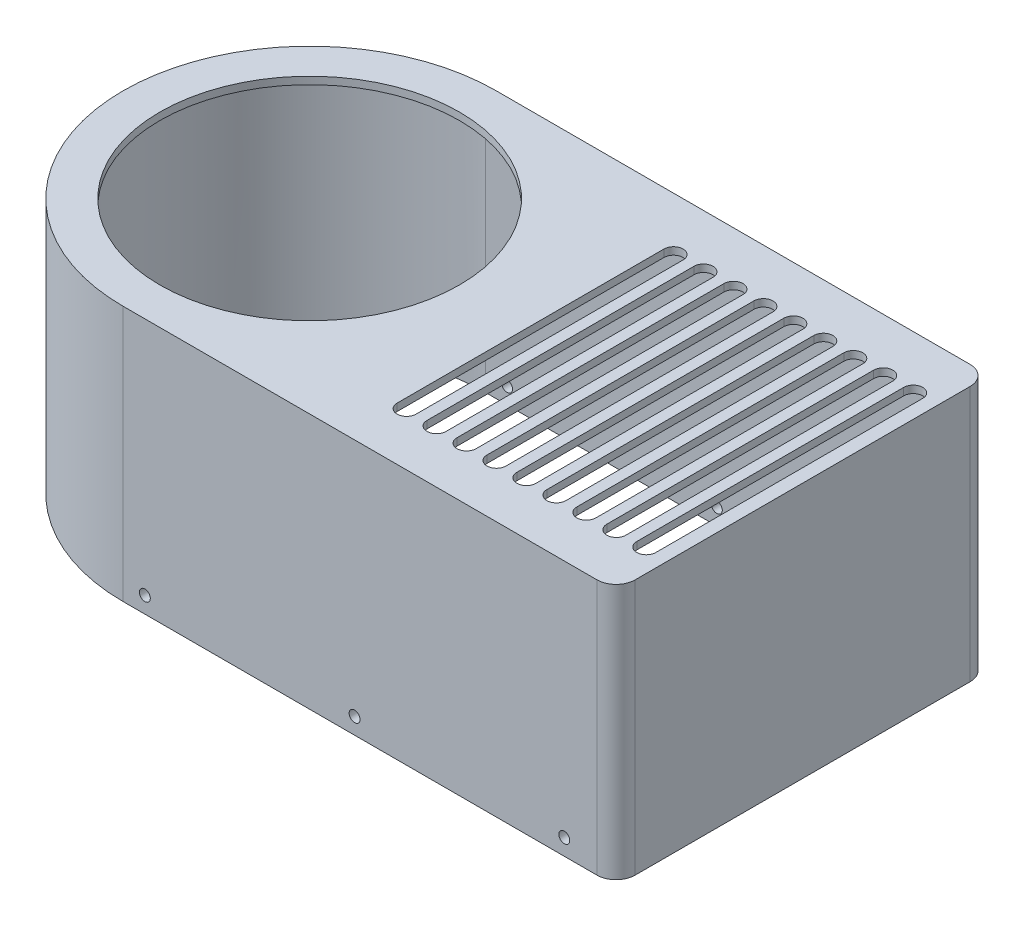
SolidWorks part; units mm, degrees
ref_plane "Front Plane" through (0, 0, 0) normal (0, 0, 1) x (1, 0, 0)
ref_plane "Top Plane" through (0, 0, 0) normal (0, 1, 0) x (1, 0, 0)
ref_plane "Right Plane" through (0, 0, 0) normal (1, 0, 0) x (0, 0, -1)
sketch "Sketch1" plane through (0, 0, 0) normal (0, 1, 0) x (1, 0, 0)
  line L0 (0, 64.5) -> (177, 64.5)
  line L1 (0, -64.5) -> (177, -64.5)
  line L2 (177, 64.5) -> (177, -64.5)
  line L3 (0, -68.5) -> (181, -68.5)
  line L4 (181, -68.5) -> (181, 68.5)
  line L5 (181, 68.5) -> (0, 68.5)
  circle A1 centre (0, 0) radius 25 construction
  arc A2 (0, 64.5) -> (0, -64.5) centre (0, 0) ccw
  arc A4 (0, -68.5) -> (0, 68.5) centre (0, 0) cw
  point P6 (181, 0)
  point P11 (177, 0)
  dimension "D1" = 4
  dimension "D2" = 50
  dimension "D3" = 129
  dimension "D4" = 177
  dimension "D5" = 4
  dimension "D6" = 4
extrude "Boss-Extrude1" add sketch "Sketch1" along normal blind 93.9
sketch "Sketch2" plane through (0, 93.9, 0) normal (0, 1, 0) x (1, 0, 0)
  line L0 (0, -64.5) -> (177, -64.5)
  line L1 (177, -64.5) -> (177, 64.5)
  line L2 (177, 64.5) -> (0, 64.5)
  arc A0 (0, 64.5) -> (0, -64.5) centre (0, 0) ccw
extrude "Boss-Extrude2" add sketch "Sketch2" against normal blind 2.7
fillet "Fillet1" radius 7 2 edges at (181, 46.95, -68.5) (181, 46.95, 68.5)
fillet "Fillet2" radius 7 2 edges at (177, 45.6, 64.5) (177, 45.6, -64.5)
sketch "Sketch3" plane through (0, 93.9, 0) normal (0, 1, 0) x (1, 0, 0)
  line L0 (181, 0) -> (172.6, 0) construction
  line L1 (181, -61.5) -> (181, 61.5) construction
  line L2 (172.6, 49) -> (172.6, -49) construction
  line L3 (176.1, 49) -> (176.1, -49)
  line L4 (169.1, 49) -> (169.1, -49)
  line L5 (150.6, 49) -> (150.6, -49) construction
  line L6 (154.1, 49) -> (154.1, -49)
  line L7 (147.1, 49) -> (147.1, -49)
  line L8 (161.6, 49) -> (161.6, -49) construction
  line L9 (165.1, 49) -> (165.1, -49)
  line L10 (158.1, 49) -> (158.1, -49)
  line L11 (139.6, 49) -> (139.6, -49) construction
  line L12 (143.1, 49) -> (143.1, -49)
  line L13 (136.1, 49) -> (136.1, -49)
  line L14 (161.6, 0) -> (172.6, 0) construction
  line L15 (150.6, 0) -> (161.6, 0) construction
  line L16 (139.6, 0) -> (150.6, 0) construction
  line L17 (128.6, 49) -> (128.6, -49) construction
  line L18 (132.1, 49) -> (132.1, -49)
  line L19 (125.1, 49) -> (125.1, -49)
  line L20 (117.6, 49) -> (117.6, -49) construction
  line L21 (121.1, 49) -> (121.1, -49)
  line L22 (114.1, 49) -> (114.1, -49)
  line L23 (106.6, 49) -> (106.6, -49) construction
  line L24 (110.1, 49) -> (110.1, -49)
  line L25 (103.1, 49) -> (103.1, -49)
  line L26 (95.6, -49) -> (95.6, 49) construction
  line L29 (139.6, 0) -> (128.6, 0) construction
  line L30 (128.6, 0) -> (117.6, 0) construction
  line L31 (117.6, 0) -> (106.6, 0) construction
  line L32 (106.6, 0) -> (95.6, 0) construction
  line L33 (92.1, -49) -> (92.1, 49)
  line L36 (99.1, -49) -> (99.1, 49)
  line L37 (84.6, -49) -> (84.6, 49) construction
  line L38 (81.1, -49) -> (81.1, 49)
  line L39 (88.1, -49) -> (88.1, 49)
  circle A0 centre (0, 0) radius 55
  arc A1 (176.1, 49) -> (169.1, 49) centre (172.6, 49) ccw
  arc A2 (169.1, -49) -> (176.1, -49) centre (172.6, -49) ccw
  arc A3 (154.1, 49) -> (147.1, 49) centre (150.6, 49) ccw
  arc A4 (147.1, -49) -> (154.1, -49) centre (150.6, -49) ccw
  arc A5 (165.1, 49) -> (158.1, 49) centre (161.6, 49) ccw
  arc A6 (158.1, -49) -> (165.1, -49) centre (161.6, -49) ccw
  arc A7 (143.1, 49) -> (136.1, 49) centre (139.6, 49) ccw
  arc A8 (136.1, -49) -> (143.1, -49) centre (139.6, -49) ccw
  arc A9 (132.1, 49) -> (125.1, 49) centre (128.6, 49) ccw
  arc A10 (125.1, -49) -> (132.1, -49) centre (128.6, -49) ccw
  arc A11 (121.1, 49) -> (114.1, 49) centre (117.6, 49) ccw
  arc A12 (114.1, -49) -> (121.1, -49) centre (117.6, -49) ccw
  arc A13 (110.1, 49) -> (103.1, 49) centre (106.6, 49) ccw
  arc A14 (103.1, -49) -> (110.1, -49) centre (106.6, -49) ccw
  arc A19 (92.1, -49) -> (99.1, -49) centre (95.6, -49) ccw
  arc A20 (99.1, 49) -> (92.1, 49) centre (95.6, 49) ccw
  arc A21 (81.1, -49) -> (88.1, -49) centre (84.6, -49) ccw
  arc A22 (88.1, 49) -> (81.1, 49) centre (84.6, 49) ccw
  point P9 (172.6, 0)
  point P17 (150.6, 0)
  point P24 (161.6, 0)
  point P31 (139.6, 0)
  point P40 (128.6, 0)
  point P47 (117.6, 0)
  point P54 (106.6, 0)
  point P61 (95.6, 0)
  point P70 (0, 0)
  point P73 (84.6, 0)
  point P78 (0, 0)
  dimension "D1" = 110
  dimension "D3" = 3.5
  dimension "D6" = 11
  dimension "D2" = 8.4
  dimension "D4" = 98
  dimension "D5" = 11
extrude "Cut-Extrude1" cut sketch "Sketch3" against normal through all
sketch "Sketch5" plane through (0, 91.2, 0) normal (0, -1, 0) x (1, 0, 0)
  line L0 (0, 64.5) -> (23.0651, 64.5)
  line L1 (0, -64.5) -> (23.0651, -64.5)
  arc A3 (0, -64.5) -> (0, 64.5) centre (0, 0) ccw
  arc A5 (23.0651, -64.5) -> (23.0651, 64.5) centre (0, 0) ccw
extrude "Boss-Extrude3" add sketch "Sketch5" along normal blind 7
chamfer "Chamfer1" distance 0.4 angle 45 2 edges at (68.5, 84.2, 0) (64.5, 84.2, 0)
sketch "Sketch9" plane through (0, 0, 64.5) normal (0, 0, -1) x (-1, 0, 0)
  line L0 (0, 3) -> (-3, 3) construction
  line L1 (-3, 3) -> (-3, 6) construction
  line L2 (-13, 3) -> (-13, 6) construction
  line L3 (-13, 3) -> (-3, 3) construction
  line L4 (-157, 3) -> (-90, 3) construction
  line L5 (-157, 3) -> (-157, 6) construction
  line L6 (-167, 3) -> (-167, 6) construction
  line L7 (-167, 3) -> (-157, 3) construction
  line L8 (-80, 3) -> (-80, 6) construction
  line L9 (-90, 3) -> (-90, 6) construction
  line L10 (-90, 3) -> (-80, 3) construction
  line L11 (-170, 3) -> (-167, 3) construction
  line L12 (-157, 3) -> (-90, 3) construction
  line L13 (-80, 3) -> (-13, 3) construction
  arc A0 (-13, 6) -> (-3, 6) centre (-8, 6) cw construction
  circle A1 centre (-8, 6) radius 2
  arc A2 (-167, 6) -> (-157, 6) centre (-162, 6) cw construction
  circle A3 centre (-162, 6) radius 2
  arc A4 (-90, 6) -> (-80, 6) centre (-85, 6) cw construction
  circle A5 centre (-85, 6) radius 2
  dimension "D3" = 5
  dimension "D4" = 4
  dimension "D1" = 3
  dimension "D2" = 3
  dimension "D5" = 3
  dimension "D6" = 3
extrude "Cut-Extrude3" cut sketch "Sketch9" against normal up to surface and the other way up to surface up to face at (87, 46.95, 68.5) other way up to face at (87, 46.95, -68.5)
